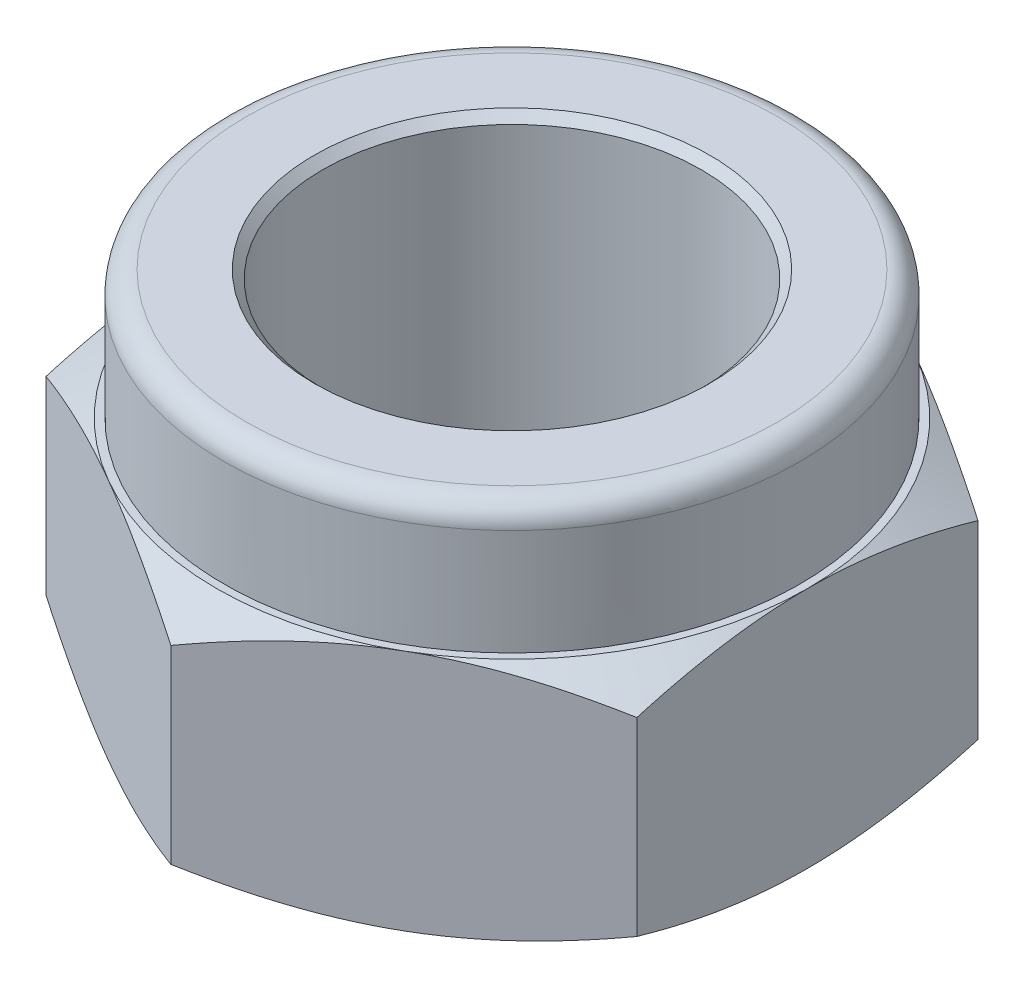
SolidWorks part; units mm, degrees
note: The reader was unsure of these and kept them because the rebuilt part matched: shared geometry of "草图2<3>", "草图2<4>".
material "AISI 304"
ref_plane "前视基准面" through (0, 0, 0) normal (0, 0, 1) x (1, 0, 0)
ref_plane "上视基准面" through (0, 0, 0) normal (0, 1, 0) x (1, 0, 0)
ref_plane "右视基准面" through (0, 0, 0) normal (1, 0, 0) x (0, 0, -1)
sketch "草图1" plane through (0, 0, 0) normal (0, 0, 1) x (1, 0, 0)
  line L0 (0, 0) -> (0, 2785.3738) construction
  line L1 (2.5, 0) -> (3.9, 0)
  line L2 (3.9, 0) -> (3.9, 3.2)
  line L3 (3.9, 3.2) -> (3.8, 3.2)
  line L4 (3.8, 3.2) -> (3.8, 4.9)
  line L5 (3.8, 4.9) -> (2.5, 4.9)
  line L6 (2.5, 4.9) -> (2.5, 0)
  dimension "六边厚度" = 3.2
  dimension "总厚度" = 4.9
  dimension "公称直径" = 5
  dimension "六边直径" = 7.8
  dimension "圆边直径" = 7.6
revolve "旋转1" add sketch "草图1" angle 360 about L0
sketch "草图2" plane through (0, 0, 0) normal (0, -1, 0) x (1, 0, 0)
  line L1 (0, 4.5033) -> (-3.9, 2.2517)
  line L2 (-3.9, 2.2517) -> (-3.9, -2.2517)
  line L3 (-3.9, -2.2517) -> (0, -4.5033)
  line L4 (0, -4.5033) -> (3.9, -2.2517)
  line L5 (3.9, -2.2517) -> (3.9, 2.2517)
  line L6 (3.9, 2.2517) -> (0, 4.5033)
  circle A0 centre (0, 0) radius 3.9
  circle A1 centre (0, 0) radius 2.5 construction
  circle A2 centre (0, 0) radius 2.5
  circle M3 centre (0, 0) radius 3.9
  circle M4 centre (0, 0) radius 2.5
  dimension "六角对边宽" = 7.8
extrude "凸台-拉伸1" add sketch "草图2" against normal up to surface (3.2 mm away) contours M3 M4 | L1 L2 M3 | L6 L1 M3 | L2 L3 M3 | L4 L5 M3 | L3 L4 M3 | A2
extrude "切除-拉伸2" cut sketch "草图2<3>" against normal blind 10 draft 60 flip side to cut contours A0
sketch "草图2<3>" plane through (0, 0, 0) normal (0, -1, 0) x (1, 0, 0) same geometry as "草图2"
extrude "切除-拉伸3" cut sketch "草图2<4>" along normal through all draft 60 from surface at -3.2 flip side to cut contours A0
sketch "草图2<4>" plane through (0, 0, 0) normal (0, -1, 0) x (1, 0, 0) same geometry as "草图2"
fillet "圆角1" radius 0.3 1 edges at (0, 4.9, -3.8)
chamfer "倒角2" distance 0.111 angle 45 2 edges at (0, 0, -2.5) (0, 4.9, -2.5)
